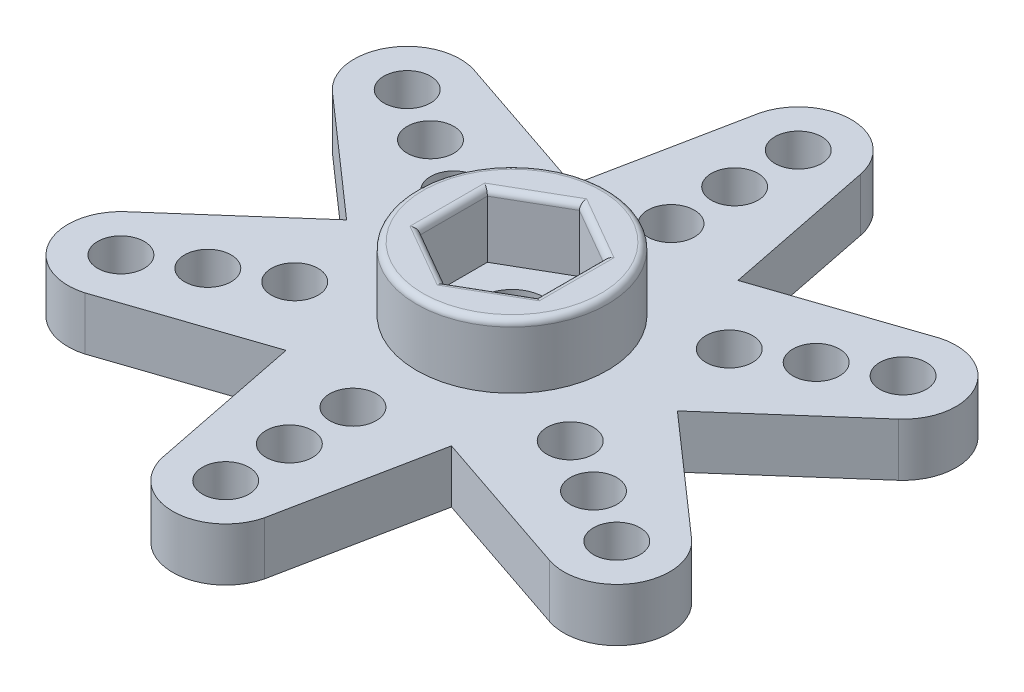
SolidWorks part; units mm, degrees
ref_plane "Alzado" through (0, 0, 0) normal (0, 0, 1) x (1, 0, 0)
ref_plane "Planta" through (0, 0, 0) normal (0, 1, 0) x (1, 0, 0)
ref_plane "Vista lateral" through (0, 0, 0) normal (1, 0, 0) x (0, 0, -1)
sketch "Croquis1" plane through (0, 0, 0) normal (0, 1, 0) x (1, 0, 0)
  line L0 (3.9, -6.755) -> (-3.9, -6.755) construction
  line L1 (0, 0) -> (0, -16) construction
  line L2 (-3.9, -6.755) -> (-10.9949, -9.151)
  line L3 (-13.342, -4.8725) -> (-7.8, 0)
  line L4 (-7.8, 0) -> (-13.4225, 4.9463)
  line L5 (-10.8907, 9.1183) -> (-3.9, 6.755)
  line L6 (-3.9, 6.755) -> (-2.4276, 14.0973)
  line L7 (2.4514, 13.9908) -> (3.9, 6.755)
  line L8 (3.9, 6.755) -> (10.9949, 9.151)
  line L9 (13.342, 4.8725) -> (7.8, 0)
  line L10 (3.9, -6.755) -> (2.4276, -14.0973)
  line L11 (7.8, 0) -> (13.4225, -4.9463)
  line L12 (-2.4514, -13.9908) -> (-3.9, -6.755)
  line L13 (10.8907, -9.1183) -> (3.9, -6.755)
  arc A0 (-13.342, -4.8725) -> (-10.9949, -9.151) centre (-11.6913, -6.75) ccw
  arc A1 (-10.8907, 9.1183) -> (-13.4225, 4.9463) centre (-11.6913, 6.75) ccw
  arc A2 (2.4514, 13.9908) -> (-2.4276, 14.0973) centre (0, 13.5) ccw
  arc A3 (13.342, 4.8725) -> (10.9949, 9.151) centre (11.6913, 6.75) ccw
  arc A4 (-2.4514, -13.9908) -> (2.4276, -14.0973) centre (0, -13.5) ccw
  arc A5 (10.8907, -9.1183) -> (13.4225, -4.9463) centre (11.6913, -6.75) ccw
  circle A6 centre (0, 0) radius 16 construction
  circle A8 centre (0, 0) radius 7.8 construction
  point P35 (0, 0)
  point P37 (0, 0)
  dimension "D1" = 32
  dimension "D5" = 5
  dimension "D2" = 15.6
extrude "Saliente-Extruir1" add sketch "Croquis1" along normal blind 2.5
sketch "Croquis2" plane through (0, 2.5, 0) normal (0, 1, 0) x (1, 0, 0)
  line L1 (0, -3.1754) -> (2.75, -1.5877)
  line L2 (2.75, -1.5877) -> (2.75, 1.5877)
  line L3 (2.75, 1.5877) -> (0, 3.1754)
  line L4 (0, 3.1754) -> (-2.75, 1.5877)
  line L5 (-2.75, 1.5877) -> (-2.75, -1.5877)
  line L6 (-2.75, -1.5877) -> (0, -3.1754)
  circle A0 centre (0, 0) radius 4.5
  circle A1 centre (0, 0) radius 3.1754 construction
  circle A2 centre (0, 0) radius 2.75 construction
  dimension "D1" = 9
  dimension "D2" = 5.5
extrude "Saliente-Extruir2" add sketch "Croquis2" along normal blind 3
sketch "Croquis3" plane through (0, 0, 0) normal (0, -1, 0) x (1, 0, 0)
  circle A0 centre (0, 0) radius 1.5
  dimension "D1" = 3
extrude "Cortar-Extruir1" cut sketch "Croquis3" against normal up to next
sketch "Croquis4" plane through (0, 0, 0) normal (0, -1, 0) x (1, 0, 0)
  circle A0 centre (0, 0) radius 2.8
  dimension "D1" = 5.6
extrude "Cortar-Extruir2" cut sketch "Croquis4" against normal offset from surface (1 mm away) 1.5 up to face at (0, 2.5, 1.5)
sketch "Croquis5" plane through (0, 0, 0) normal (0, -1, 0) x (1, 0, 0)
  circle A0 centre (0, 0) radius 4.5
  circle A1 centre (0, 0) radius 3.5
  dimension "D1" = 9
  dimension "D2" = 7
extrude "Cortar-Extruir3" cut sketch "Croquis5" against normal blind 0.5
fillet "Redondeo1" radius 0.3 10 edges at (0, 0, -4.5) (0, 0, -2.8) (0, 0, -3.5) (0, 5.5, 4.5) (2.75, 5.5, 0) (1.375, 5.5, 2.3816) (-1.375, 5.5, 2.3816) (-2.75, 5.5, 0) (-1.375, 5.5, -2.3816) (1.375, 5.5, -2.3816)
sketch "Croquis6" plane through (0, 0, 0) normal (0, -1, 0) x (1, 0, 0)
  line L0 (0, 0) -> (0, -16.5) construction
  circle A0 centre (0, 0) radius 10.5 construction
  circle A1 centre (0, 0) radius 13.5 construction
  circle A3 centre (0, 0) radius 7.5 construction
  circle A5 centre (0, -13.5) radius 1.1
  circle A6 centre (0, -10.5) radius 1.1
  circle A7 centre (0, -7.5) radius 1.1
  dimension "D2" = 27
  dimension "D3" = 21
  dimension "D4" = 15
extrude "Cortar-Extruir4" cut sketch "Croquis6" against normal up to next
pattern_circular "MatrizC1" count 6 over 360 about axis through (0, 1, 0) along (0, -1, 0) of "Cortar-Extruir4"
